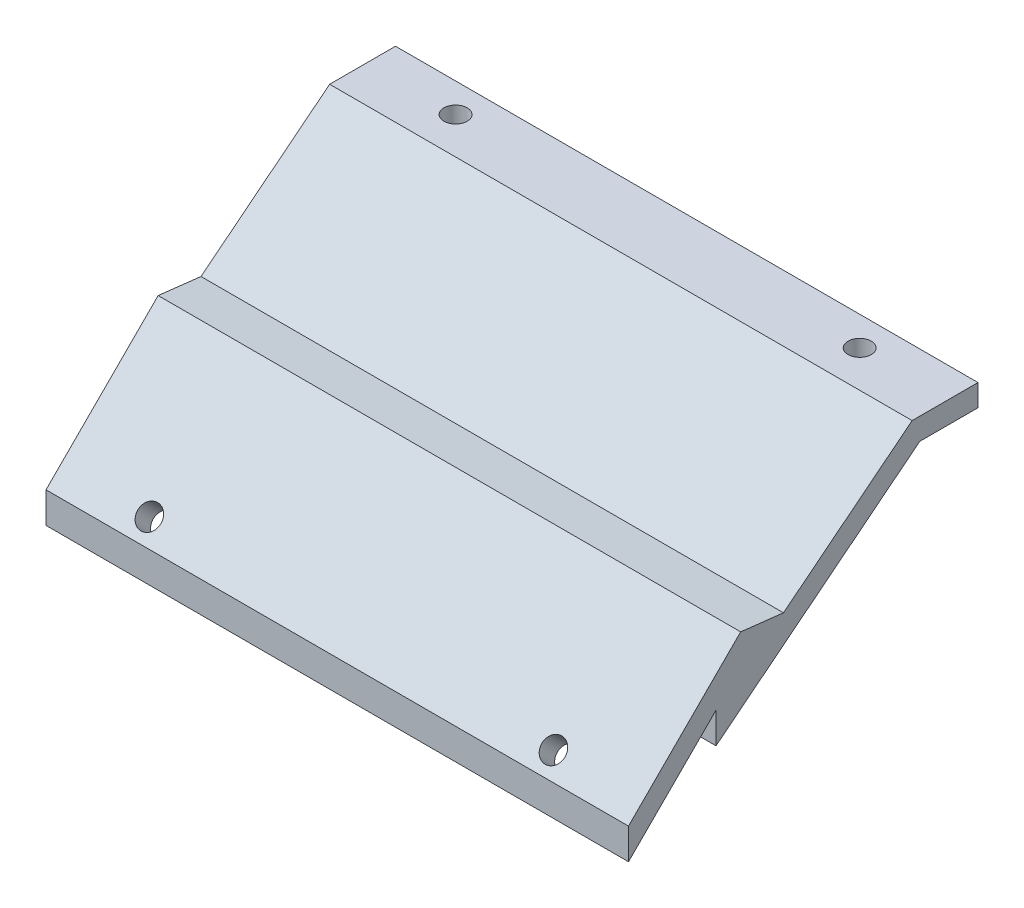
SolidWorks part; units mm, degrees
ref_plane "Front Plane" through (0, 0, 0) normal (0, 0, 1) x (1, 0, 0)
ref_plane "Top Plane" through (0, 0, 0) normal (0, 1, 0) x (1, 0, 0)
ref_plane "Right Plane" through (0, 0, 0) normal (1, 0, 0) x (0, 0, -1)
sketch "Sketch1" plane through (0, 0, 0) normal (1, 0, 0) x (0, 0, -1)
  line L0 (0, 0) -> (0, -4.2426)
  line L4 (0, 0) -> (15.0208, 15.0208)
  line L5 (15.0208, 15.0208) -> (15.0208, 9.7515)
  line L6 (15.0208, 9.7515) -> (40, 29.5883)
  line L7 (40, 29.5883) -> (40, 25.7574)
  line L8 (40, 25.7574) -> (12.0208, 3.5382)
  line L9 (12.0208, 3.5382) -> (12.0208, 7.7782)
  line L10 (12.0208, 7.7782) -> (0, -4.2426)
  line L11 (0, -4.2426) -> (12.0208, -4.2426) construction
  dimension "D1" = 45
  dimension "D2" = 17
  dimension "D3" = 3
  dimension "D4" = 3
  dimension "D5" = 3
  dimension "D6" = 4.24
  dimension "D7" = 40
  dimension "D8" = 30
extrude "Boss-Extrude1" add sketch "Sketch1" along normal mid plane 80
sketch "Sketch2" plane through (0, -2.1213, -2.1213) normal (0, -0.7071, -0.7071) x (1, 0, 0)
  line L0 (0, -14) -> (0, -2.75) construction
  line L1 (-27.75, -2.75) -> (27.75, -2.75) construction
  line L5 (40, -14) -> (-40, -14) construction
  circle A0 centre (-27.75, -2.75) radius 1.6
  circle A1 centre (27.75, -2.75) radius 1.6
  point P9 (0, -2.75)
  dimension "D3" = 3.2
  dimension "D1" = 11.25
  dimension "D2" = 55.5
extrude "Cut-Extrude1" cut sketch "Sketch2" against normal up to surface (3 mm away) up to face at (0, 7.5104, -7.5104)
sketch "Sketch3" plane through (0, 0, -40) normal (0, 0, -1) x (-1, 0, 0)
  line L4 (-40, 3.5382) -> (-40, 25.7574) construction
  line L5 (-40, 28.7574) -> (40, 28.7574)
  line L6 (-40, 28.7574) -> (-40, 25.7574)
  line L7 (-40, 25.7574) -> (40, 25.7574)
  line L8 (40, 28.7574) -> (40, 25.7574)
  line L9 (-40, 28.7574) -> (40, 25.7574) construction
  line L10 (-40, 25.7574) -> (40, 28.7574) construction
  point P0 (0, 27.2574)
  dimension "D1" = 3
extrude "Boss-Extrude2" add sketch "Sketch3" along normal blind 8
sketch "Sketch4" plane through (0, 0, -40) normal (0, 0, -1) x (-1, 0, 0)
  line L0 (-40, 29.5883) -> (-40, 28.7574)
  line L1 (-40, 28.7574) -> (40, 28.7574)
  line L2 (40, 28.7574) -> (40, 29.5883)
  line L3 (40, 29.5883) -> (-40, 29.5883)
extrude "Cut-Extrude2" cut sketch "Sketch4" against normal through all
chamfer "Chamfer1" distance 8 angle 45 1 edges at (0, 9.7515, -15.0208) first distance on face at (0, 19.2544, -26.9873)
sketch "Sketch5" plane through (0, 25.7574, 0) normal (0, -1, 0) x (1, 0, 0)
  line L0 (-40, -44) -> (40, -44) construction
  line L1 (-40, -48) -> (-40, -40) construction
  line L2 (40, -48) -> (40, -40) construction
  line L3 (-27.75, -5.1972) -> (-27.75, -48) construction
  line L4 (40, -48) -> (-40, -48) construction
  line L5 (27.75, -5.1972) -> (27.75, -48) construction
  circle A0 centre (-27.75, -44) radius 1.6
  circle A1 centre (27.75, -44) radius 1.6
  ellipse E0 centre (-27.75, -4.0659) end of major axis (-29.35, -4.0659) minor radius 1.1314 construction
  ellipse E1 centre (27.75, -4.0659) end of major axis (26.15, -4.0659) minor radius 1.1314 construction
  dimension "D1" = 3.2
extrude "Cut-Extrude3" cut sketch "Sketch5" against normal up to surface (3 mm away) up to face at (0, 28.7574, -43.4768)
